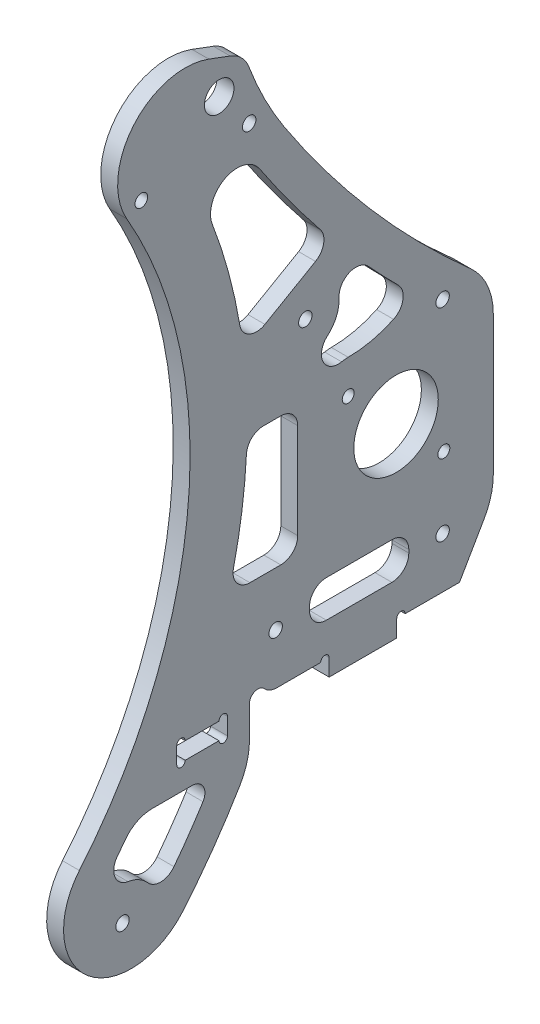
SolidWorks part; units mm, degrees
material "8619K441 HDPE"
ref_plane "Front" through (0, 0, 0) normal (0, 0, 1) x (1, 0, 0)
ref_plane "Top" through (0, 0, 0) normal (0, 1, 0) x (1, 0, 0)
ref_plane "Right" through (0, 0, 0) normal (1, 0, 0) x (0, 0, -1)
sketch "Sketch1" plane through (0, 0, 0) normal (1, 0, 0) x (0, 0, -1)
  line L0 (0, 50.8) -> (0, 177.8) construction
  line L1 (0, 0) -> (153.9793, 88.9) construction
  line L2 (0, 0) -> (136.2027, -114.2876) construction
  circle A0 centre (0, 0) radius 50.8 construction
  circle A1 centre (0, 0) radius 177.8 construction
  dimension "D1" = 101.6
  dimension "D2" = 127
  dimension "D3" = 60
  dimension "D4" = 70
sketch "Sketch2" plane through (0, 0, 0) normal (1, 0, 0) x (0, 0, -1)
  line L0 (0, 0) -> (136.2027, -114.2876) construction
  line L1 (0, 0) -> (153.9793, 88.9) construction
  line L2 (184.8616, 125.3952) -> (192.8882, 122.3981)
  line L3 (200.1102, -98.3) -> (200.1102, -91.95) construction
  line L4 (291.7282, -10.95) -> (291.7282, -63.147)
  line L5 (201.6071, -91.95) -> (188.9071, -91.95) construction
  line L6 (279.0282, -91.95) -> (258.6192, -91.95)
  line L7 (200.1102, -91.95) -> (200.1102, -110.5163)
  line L8 (279.0282, -91.95) -> (288.3253, -75.847)
  line L9 (255.4442, -91.95) -> (255.4442, -98.3)
  line L10 (255.4442, -98.3) -> (230.0442, -98.3)
  line L11 (230.0442, -98.3) -> (230.0442, -91.95)
  line L12 (226.8692, -91.95) -> (206.4602, -91.95)
  line L13 (255.4442, -98.3) -> (257.0823, -98.3) construction
  arc A0 (153.9793, 88.9) -> (136.2027, -114.2876) centre (0, 0) cw
  arc A1 (136.2027, -114.2876) -> (175.1178, -146.9412) centre (155.6602, -130.6144) ccw
  arc A2 (184.8616, 125.3952) -> (153.9793, 88.9) centre (175.9764, 101.6) ccw
  arc A4 (175.1178, -146.9412) -> (200.1102, -110.5163) centre (0, 0) ccw
  arc A5 (213.1653, 89.1967) -> (283.2016, 8.0355) centre (553.1762, 311.803) ccw
  circle A8 centre (272.6782, -10.95) radius 2.0828 construction
  circle A10 centre (188.7254, 111.25) radius 5.5499
  arc A11 (199.868, 115.4274) -> (192.8882, 122.3981) centre (188.7254, 111.25) ccw
  circle A12 centre (188.7254, 111.25) radius 11.8999 construction
  arc A13 (199.868, 115.4274) -> (213.1653, 89.1967) centre (324.7314, 162.2394) ccw
  arc A16 (175.1178, -146.9412) -> (200.1102, -110.5163) centre (0, 0) ccw
  circle A17 centre (188.7254, 111.25) radius 5.5499 construction
  arc A19 (283.2016, 8.0355) -> (291.7282, -10.95) centre (266.3282, -10.95) cw
  circle A23 centre (272.6782, -10.95) radius 1.4875 construction
  arc A24 (288.3253, -75.847) -> (291.7282, -63.147) centre (266.3282, -63.147) ccw
  circle A25 centre (242.7442, -91.95) radius 36.284 construction
  arc A26 (258.6192, -91.95) -> (255.4442, -91.95) centre (257.0317, -91.95) ccw
  arc A27 (230.0442, -91.95) -> (226.8692, -91.95) centre (228.4567, -91.95) ccw
  arc A28 (206.4602, -91.95) -> (200.1102, -91.95) centre (203.2852, -91.95) ccw
  point P38 (279.0282, -91.95)
  point P48 (291.7282, 0.6665)
  point P51 (291.7282, -91.95)
  point P56 (242.7442, -98.3)
  dimension "D1" = 50.8
  dimension "D2" = 6.35
  dimension "D3" = 406.4
  dimension "D7" = 133.35
  dimension "D8" = 25.4
  dimension "D12" = 25.4
  dimension "D13" = 3.175
  dimension "D4" = 60
  dimension "D5" = 19.05
  dimension "D10" = 6.35
  dimension "D14" = 25.4
  dimension "D6" = 6.35
extrude "Boss-Extrude1" add sketch "Sketch2" against normal mid plane 6.35 contours A5 A4 A2 A0 A1 L6 L4 region at (0, -20.5804, -211.4913)
ref_axis "Axis1" through (80.9, 0, 0) along (-1, 0, 0)
sketch "Sketch3" plane through (0, 0, 0) normal (1, 0, 0) x (0, 0, -1)
  line L0 (0, 0) -> (136.2027, -114.2876) construction
  line L1 (130.2602, -123.2847) -> (130.2602, -222.1813) construction
  line L2 (41.3602, -174.6) -> (41.3602, -61.9407) construction
  circle A0 centre (41.3602, -174.6) radius 88.9 construction
  circle A1 centre (87.5589, -73.4706) radius 63.5 construction
  circle A2 centre (0, 0) radius 50.8 construction
  arc A3 (136.2027, -114.2876) -> (175.1178, -146.9412) centre (155.6602, -130.6144) ccw construction
  circle A4 centre (0, 0) radius 177.8 construction
  dimension "D1" = 177.8
ref_plane "Plane1" through (0, 0, 0) normal (1, 0, 0) x (0, 0, -1)
sketch "Sketch4" plane through (-3.175, 0, 0) normal (-1, 0, 0) x (0, 0, 1)
  line L2 (0, 0) -> (-136.2027, -114.2876) construction
  line L3 (0, 0) -> (-153.9793, 88.9) construction
  circle A0 centre (-159.4786, 92.075) radius 2.3812 construction
  arc A1 (-142.8912, -119.9) -> (-139.2429, -116.8387) centre (-141.0671, -118.3693) ccw
  arc A2 (-167.2301, 82.6317) -> (-142.8912, -119.9) centre (0, 0) ccw
  arc A3 (-158.2746, 94.1295) -> (-139.5247, -120.1835) centre (0, 0) ccw construction
  arc A4 (-162.9604, 80.522) -> (-139.2429, -116.8387) centre (0, 0) ccw
  circle A5 centre (-159.4786, 92.075) radius 9.525 construction
  arc A6 (-162.9604, 80.522) -> (-167.2301, 82.6317) centre (-165.0953, 81.5768) ccw
  arc A7 (-158.2746, 94.1295) -> (-139.5247, -120.1835) centre (0, 0) ccw construction
  arc A8 (-150.3407, -110.4155) -> (-146.5022, -107.5964) centre (-148.4214, -109.006) ccw construction
  dimension "D1" = 19.05
extrude "Cut-Extrude1" cut sketch "Sketch4" against normal blind 3.175
sketch "Sketch32" plane through (-3.175, 0, 0) normal (-1, 0, 0) x (0, 0, 1)
  circle A0 centre (-159.4786, 92.075) radius 2.3812
  circle A1 centre (-159.4786, 92.075) radius 2.3812 construction
extrude "Cut-Extrude6" cut sketch "Sketch32" against normal through all both and the other way through all
ref_plane "Top Of Shooter" through (0, 127, 0) normal (0, 1, 0) x (1, 0, 0)
sketch "Sketch23" plane through (3.175, 0, 0) normal (1, 0, 0) x (0, 0, -1)
  line L0 (191.834, -91.95) -> (191.834, -98.3)
  line L2 (172.784, -91.95) -> (172.784, -98.3)
  line L6 (175.959, -91.95) -> (188.659, -91.95)
  line L7 (201.6071, -91.95) -> (188.9071, -91.95) construction
  line L9 (175.959, -98.3) -> (188.659, -98.3)
  line L15 (255.4442, -98.3) -> (257.0823, -98.3) construction
  line L17 (172.784, -91.95) -> (172.784, -98.3) construction
  line L22 (191.834, -91.95) -> (191.834, -98.3) construction
  arc A0 (175.959, -91.95) -> (172.784, -91.95) centre (174.3715, -91.95) ccw
  arc A2 (191.834, -91.95) -> (188.659, -91.95) centre (190.2465, -91.95) ccw
  arc A3 (172.784, -98.3) -> (175.959, -98.3) centre (174.3715, -98.3) ccw
  arc A4 (188.659, -98.3) -> (191.834, -98.3) centre (190.2465, -98.3) ccw
  dimension "D1" = 3.175
extrude "Cut-Extrude4" cut sketch "Sketch23" against normal through all
hole_wizard "1 (1) Diameter Hole1" positions "Sketch24" profile "Sketch25" hole size "1" standard "ANSI Inch" end condition through all
sketch "Sketch24" plane through (3.175, 0, 0) normal (1, 0, 0) x (0, 0, -1)
  circle A0 centre (255.1782, -28.45) radius 19.1008 construction
  point P0 (255.1782, -28.45)
sketch "Sketch25" plane through (3.175, -28.45, -255.1782) normal (0, 1, 0) x (0, 0, -1)
  line L0 (0, 0) -> (0, 6.35)
  line L1 (0, 6.35) -> (15.875, 6.35)
  line L2 (15.875, 6.35) -> (15.875, 0)
  line L5 (15.875, 0) -> (0, 0)
  line L11 (0, -6.35) -> (0, 107.95) construction
  dimension "Thru Hole Dia." = 31.75
  dimension "Thru Hole Depth" = 6.35
hole_wizard "#8 Clearance Hole1" positions "Sketch29" profile "Sketch30" hole size "#8" standard "ANSI Inch" end condition through all
sketch "Sketch29" plane through (-3.175, 0, 0) normal (-1, 0, 0) x (0, 0, 1)
  point P0 (-273.1387, -46.4105)
  point P3 (-237.2177, -10.4895)
sketch "Sketch30" plane through (-3.175, -46.4105, -273.1387) normal (0, 1, 0) x (0, 0, 1)
  line L0 (0, 0) -> (0, 6.35)
  line L1 (0, 6.35) -> (2.2479, 6.35)
  line L2 (2.2479, 6.35) -> (2.2479, 0)
  line L5 (2.2479, 0) -> (0, 0)
  line L11 (0, -6.35) -> (0, 107.95) construction
  dimension "Thru Hole Dia." = 4.4958
  dimension "Thru Hole Depth" = 6.35
sketch "Sketch31" plane through (3.175, 0, 0) normal (1, 0, 0) x (0, 0, -1)
  line L0 (237.6782, -51.1053) -> (273.1387, -51.1053) construction
  line L1 (272.6782, -5.7947) -> (237.2177, -5.7947) construction
  line L2 (237.6782, -51.1053) -> (273.1387, -51.1053) construction
  line L3 (272.6782, -5.7947) -> (237.2177, -5.7947) construction
  line L4 (277.8335, -10.95) -> (277.8335, -46.4105) construction
  line L6 (232.5229, -45.95) -> (232.5229, -10.4895) construction
  line L8 (237.6782, -52.6928) -> (273.1387, -52.6928)
  line L9 (279.421, -10.95) -> (279.421, -46.4105)
  line L10 (272.6782, -4.2072) -> (237.2177, -4.2072)
  line L11 (230.9354, -45.95) -> (230.9354, -10.4895)
  arc A0 (273.1387, -51.1053) -> (277.8335, -46.4105) centre (273.1387, -46.4105) ccw construction
  arc A1 (232.5229, -45.95) -> (237.6782, -51.1053) centre (237.6782, -45.95) ccw construction
  arc A2 (237.2177, -5.7947) -> (232.5229, -10.4895) centre (237.2177, -10.4895) ccw construction
  arc A3 (277.8335, -10.95) -> (272.6782, -5.7947) centre (272.6782, -10.95) ccw construction
  arc A12 (273.1387, -51.1053) -> (277.8335, -46.4105) centre (273.1387, -46.4105) ccw construction
  arc A15 (232.5229, -45.95) -> (237.6782, -51.1053) centre (237.6782, -45.95) ccw construction
  arc A16 (237.2177, -5.7947) -> (232.5229, -10.4895) centre (237.2177, -10.4895) ccw construction
  arc A17 (277.8335, -10.95) -> (272.6782, -5.7947) centre (272.6782, -10.95) ccw construction
  arc A18 (230.9354, -45.95) -> (237.6782, -52.6928) centre (237.6782, -45.95) ccw
  arc A19 (273.1387, -52.6928) -> (279.421, -46.4105) centre (273.1387, -46.4105) ccw
  arc A20 (279.421, -10.95) -> (272.6782, -4.2072) centre (272.6782, -10.95) ccw
  arc A21 (237.2177, -4.2072) -> (230.9354, -10.4895) centre (237.2177, -10.4895) ccw
  dimension "D1" = 1.5875
extrude "Cut-Extrude5" [suppressed] cut sketch "Sketch31" against normal through all
fillet "Fillet1" radius 25.4 1 edges at (0, -110.5163, -200.1102)
fillet "Fillet2" radius 6.35 1 edges at (0, -91.95, -206.4602)
sketch "Sketch34" plane through (-3.175, 0, 0) normal (-1, 0, 0) x (0, 0, 1)
  line L0 (-272.6782, -72.9) -> (-209.9539, -72.9) construction
  line L1 (-279.0282, -91.95) -> (-258.6192, -91.95) construction
  line L2 (-291.7282, -10.95) -> (-291.7282, -63.147) construction
  line L3 (-221.0918, 22.6605) -> (0, 0) construction
  line L4 (0, 0) -> (-200.0079, 96.9118) construction
  line L5 (-209.9539, -72.9) -> (0, 0) construction
  line L6 (-149.6877, -147.0238) -> (-159.5027, -120.0573) construction
  line L7 (-149.6877, -147.0238) -> (-146.9729, -154.4826) construction
  circle A0 centre (0, 0) radius 222.25 construction
  circle A1 centre (-272.6782, -72.9) radius 3.9687
  circle A2 centre (-272.6782, 3.3) radius 3.9687
  circle A3 centre (-209.9539, -72.9) radius 3.9688
  circle A4 centre (-221.0918, 22.6605) radius 3.9687
  circle A5 centre (-200.0079, 96.9118) radius 3.9687
  circle A6 centre (-149.6877, -147.0238) radius 7.9375 construction
  arc A7 (-175.1178, -146.9412) -> (-136.2027, -114.2876) centre (-155.6602, -130.6144) ccw construction
  circle A11 centre (-152.4025, -139.565) radius 3.9687
  dimension "D1" = 7.9375
  dimension "D4" = 444.5
  dimension "D8" = 15.875
  dimension "D2" = 19.05
  dimension "D3" = 19.05
  dimension "D5" = 25
  dimension "D6" = 20
  dimension "D7" = 76.2
  dimension "D9" = 70
extrude "Cut-Extrude7" cut sketch "Sketch34" against normal up to surface (1.7463 mm away)
sketch "Sketch35" plane through (3.175, 0, 0) normal (1, 0, 0) x (0, 0, -1)
  circle A0 centre (152.4025, -139.565) radius 3.9687 construction
  circle A1 centre (200.0079, 96.9118) radius 3.9687
  circle A2 centre (200.0079, 96.9118) radius 3.9688
  circle A3 centre (221.0918, 22.6605) radius 3.9687
  circle A4 centre (221.0918, 22.6605) radius 3.9687
  circle A5 centre (209.9539, -72.9) radius 3.9688
  circle A6 centre (209.9539, -72.9) radius 3.9687
  circle A7 centre (272.6782, 3.3) radius 3.9687
  circle A8 centre (272.6782, 3.3) radius 3.9687
  circle A9 centre (272.6782, -72.9) radius 3.9687
  circle A10 centre (272.6782, -72.9) radius 3.9687
  circle A11 centre (152.4025, -139.565) radius 3.9687
  dimension "D1" = 0
  dimension "D2" = 0
  dimension "D3" = 0
  dimension "D4" = 0
  dimension "D5" = 0
extrude "Cut-Extrude8" [suppressed] cut sketch "Sketch35" against normal up to surface (1.7463 mm away)
hole_wizard "#8 (0.199) Diameter Hole1" positions "Sketch36" profile "Sketch37" hole size "#8" standard "ANSI Inch" end condition through all
sketch "Sketch36" plane through (3.175, 0, 0) normal (1, 0, 0) x (0, 0, -1)
  point P1 (272.6782, -72.9)
  point P3 (209.9539, -72.9)
  point P5 (221.0918, 22.6605)
  point P7 (200.0079, 96.9118)
  point P9 (272.6782, 3.3)
  point P22 (152.4025, -139.565)
sketch "Sketch37" plane through (3.175, -72.9, -272.6782) normal (0, 1, 0) x (0, 0, -1)
  line L0 (0, 0) -> (0, 6.35)
  line L1 (0, 6.35) -> (2.5273, 6.35)
  line L2 (2.5273, 6.35) -> (2.5273, 0)
  line L5 (2.5273, 0) -> (0, 0)
  line L11 (0, -6.35) -> (0, 107.95) construction
  dimension "Thru Hole Dia." = 5.0546
  dimension "Thru Hole Depth" = 6.35
sketch "Sketch38" plane through (3.175, 0, 0) normal (1, 0, 0) x (0, 0, -1)
  line L0 (205.9148, 28.5628) -> (224.9244, 39.538)
  line L1 (0, 0) -> (68.7087, 0) construction
  line L2 (205.31, -4.2072) -> (211.8854, -4.2072)
  line L3 (218.2354, -10.5572) -> (218.2354, -46.3428)
  line L4 (211.8854, -52.6928) -> (200.2898, -52.6928)
  line L5 (226.8692, -91.95) -> (210.3847, -91.95) construction
  line L6 (229.0039, -65.3928) -> (253.6282, -65.3928)
  line L7 (237.6782, -52.6928) -> (273.1387, -52.6928) construction
  line L8 (272.6782, -4.2072) -> (237.2177, -4.2072) construction
  line L9 (230.9354, -45.95) -> (230.9354, -10.4895) construction
  line L10 (222.6539, -71.7428) -> (222.6539, -72.9)
  line L11 (229.0039, -79.25) -> (253.6282, -79.25)
  line L12 (259.9782, -71.7428) -> (259.9782, -72.9)
  line L13 (178.6144, -107.825) -> (163.597, -107.825)
  line L15 (175.959, -98.3) -> (188.659, -98.3) construction
  arc A0 (196.4776, 33.01) -> (186.1427, 71.0211) centre (0, 0) ccw
  arc A1 (167.2301, 82.6317) -> (142.8912, -119.9) centre (0, 0) ccw construction
  arc A2 (194.1032, -44.9114) -> (200.2898, -52.6928) centre (200.2898, -46.3428) ccw
  arc A3 (229.3521, 13.014) -> (233.7726, 23.3584) centre (221.0918, 22.6605) ccw
  arc A4 (202.54, 82.2402) -> (274.7649, -1.4573) centre (553.1762, 311.803) ccw
  arc A5 (203.9107, 80.16) -> (226.696, 49.0188) centre (553.1762, 311.803) ccw
  circle A6 centre (200.0079, 96.9118) radius 12.7 construction
  arc A7 (203.9107, 80.16) -> (186.1427, 71.0211) centre (195.534, 74.6043) ccw
  arc A8 (224.9244, 39.538) -> (226.696, 49.0188) centre (221.7494, 45.0372) ccw
  arc A9 (196.4776, 33.01) -> (205.9148, 28.5628) centre (202.7398, 34.0621) ccw
  arc A10 (194.1032, -44.9114) -> (198.9684, -10.2311) centre (0, 0) ccw
  arc A11 (218.2354, -46.3428) -> (211.8854, -52.6928) centre (211.8854, -46.3428) cw
  arc A12 (211.8854, -4.2072) -> (218.2354, -10.5572) centre (211.8854, -10.5572) cw
  arc A13 (198.9684, -10.2311) -> (205.31, -4.2072) centre (205.31, -10.5572) cw
  circle A14 centre (209.9539, -72.9) radius 12.7 construction
  circle A15 centre (272.6782, -72.9) radius 12.7 construction
  arc A16 (253.6282, -79.25) -> (259.9782, -72.9) centre (253.6282, -72.9) ccw
  arc A17 (253.6282, -65.3928) -> (259.9782, -71.7428) centre (253.6282, -71.7428) cw
  arc A18 (229.0039, -65.3928) -> (222.6539, -71.7428) centre (229.0039, -71.7428) ccw
  arc A19 (222.6539, -72.9) -> (229.0039, -79.25) centre (229.0039, -72.9) ccw
  arc A20 (237.2177, 2.2105) -> (234.7275, 1.964) centre (237.2177, -10.4895) ccw
  circle A21 centre (272.6782, 3.3) radius 12.7 construction
  arc A23 (256.0295, 16.2549) -> (244.7856, 28.0072) centre (553.1762, 311.803) cw
  arc A24 (229.3521, 13.014) -> (234.7275, 1.964) centre (233.4823, 8.1907) ccw
  arc A25 (237.2177, 2.2105) -> (254.2446, 6.0377) centre (237.2177, 41.9997) ccw
  arc A26 (244.7856, 28.0072) -> (233.7726, 23.3584) centre (240.113, 23.7073) ccw
  arc A28 (254.2446, 6.0377) -> (256.0295, 16.2549) centre (251.5273, 11.7769) ccw
  arc A29 (161.9335, -131.1716) -> (154.4383, -127.0292) centre (152.4025, -139.565) ccw
  arc A30 (182.6433, -115.1271) -> (171.7505, -130.8226) centre (0, 0) cw
  arc A32 (153.3721, -112.9922) -> (150.4414, -116.8658) centre (0, 0) cw
  arc A33 (136.2027, -114.2876) -> (153.9793, 88.9) centre (0, 0) ccw construction
  arc A34 (175.1178, -146.9412) -> (196.549, -116.7324) centre (0, 0) ccw construction
  arc A35 (150.4414, -116.8658) -> (154.4383, -127.0292) centre (155.4562, -120.7614) ccw
  arc A36 (178.6144, -107.825) -> (182.6433, -115.1271) centre (178.6144, -112.5875) cw
  arc A37 (171.7505, -130.8226) -> (161.9335, -131.1716) centre (166.6991, -126.9749) cw
  arc A38 (163.597, -107.825) -> (153.3721, -112.9922) centre (163.597, -120.525) ccw
  dimension "D1" = 12.7
  dimension "D3" = 25.4
  dimension "D5" = 6.35
  dimension "D6" = 12.7
  dimension "D7" = 6.35
  dimension "D10" = 6.35
  dimension "D11" = 12.7
  dimension "D12" = 12.7
  dimension "D13" = 6.35
  dimension "D14" = 25.4
  dimension "D16" = 12.7
  dimension "D17" = 12.7
  dimension "D18" = 4.7625
  dimension "D19" = 6.35
  dimension "D20" = 12.7
  dimension "D21" = 6.35
  dimension "D4" = 30
  dimension "D8" = 12.7
  dimension "D9" = 12.7
  dimension "D15" = 9.525
  dimension "D2" = 12.7
extrude "Cut-Extrude9" cut sketch "Sketch38" against normal through all
